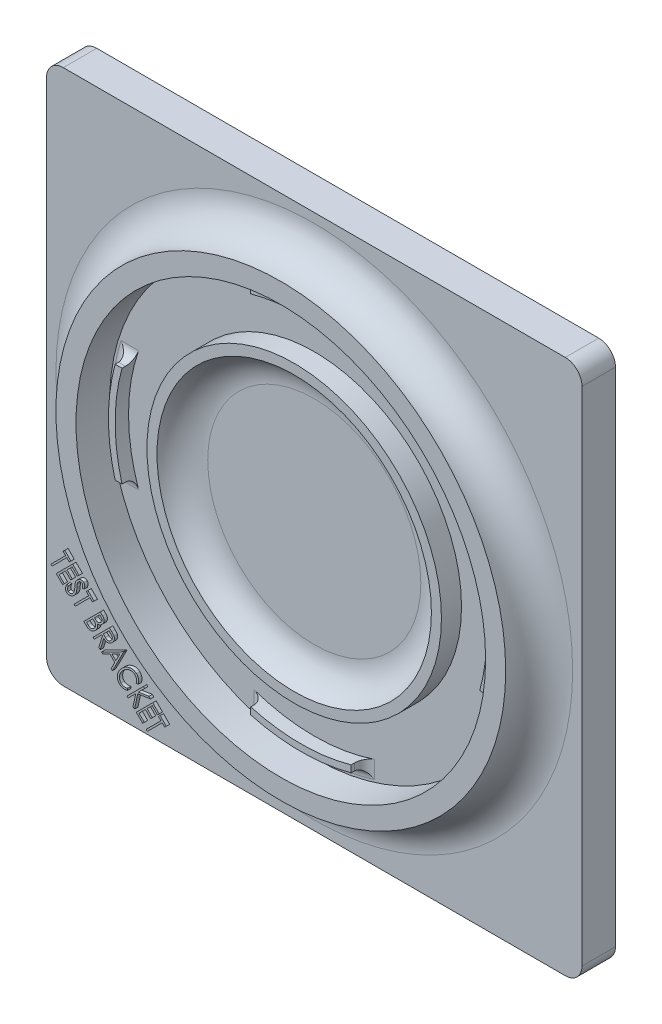
SolidWorks part; units mm, degrees
ref_plane "Front Plane" through (0, 0, 0) normal (0, 0, 1) x (1, 0, 0)
ref_plane "Top Plane" through (0, 0, 0) normal (0, 1, 0) x (1, 0, 0)
ref_plane "Right Plane" through (0, 0, 0) normal (1, 0, 0) x (0, 0, -1)
sketch "Sketch1" plane through (0, 0, 0) normal (0, 0, 1) x (1, 0, 0)
  line L1 (-40, 40) -> (40, 40)
  line L2 (-40, 40) -> (-40, -40)
  line L3 (-40, -40) -> (40, -40)
  line L4 (40, 40) -> (40, -40)
  line L5 (-40, 40) -> (40, -40) construction
  line L6 (-40, -40) -> (40, 40) construction
  point P0 (0, 0)
  dimension "D1" = 80
  dimension "D2" = 80
extrude "Boss-Extrude1" add sketch "Sketch1" along normal blind 5
fillet "Fillet1" radius 2.5 4 edges at (40, 40, 2.5) (-40, 40, 2.5) (40, -40, 2.5) (-40, -40, 2.5)
sketch "Sketch5" plane through (0, 0, 5) normal (0, 0, 1) x (1, 0, 0)
  line L5 (0, 29) -> (0, 27.75) construction
  line L6 (-7.5, 29) -> (7.5, 29)
  line L11 (-7.5, 29) -> (-7.5, -29)
  line L12 (-7.5, -29) -> (7.5, -29)
  line L16 (7.5, 29) -> (7.5, -29)
  line L17 (-7.5, 29) -> (7.5, -29) construction
  line L18 (-7.5, -29) -> (7.5, 29) construction
  line L19 (-29, 7.5) -> (29, 7.5)
  line L20 (-29, 7.5) -> (-29, -7.5)
  line L21 (-29, -7.5) -> (29, -7.5)
  line L22 (29, 7.5) -> (29, -7.5)
  line L23 (-29, 7.5) -> (29, -7.5) construction
  line L24 (-29, -7.5) -> (29, 7.5) construction
  line L26 (-2, 29.0722) -> (2, 29.0722)
  line L27 (-2, 29.0722) -> (-2, 27.6778)
  line L28 (-2, 27.6778) -> (2, 27.6778)
  line L29 (2, 29.0722) -> (2, 27.6778)
  line L30 (-2, 29.0722) -> (2, 27.6778) construction
  line L31 (-2, 27.6778) -> (2, 29.0722) construction
  circle A8 centre (0, 0) radius 27.75
  circle A9 centre (0, 0) radius 28.75
  point P14 (0, 28.375)
  dimension "D1" = 57.5
  dimension "D2" = 55.5
  dimension "D3" = 15
  dimension "D4" = 58
  dimension "D5" = 15
  dimension "D6" = 58
  dimension "D7" = 4
extrude "Boss-Extrude5" add sketch "Sketch5" along normal blind 2 contours L19 A9 L21 A8 | L27 A9 L11 A8 | L16 A9 L29 A8 | A9 L19 A8 L21 | L11 A9 L16 A8 region at (-4.7656, 27.7983, 5) region at (-27.9111, 0, 5) region at (4.7656, 27.7983, 5) region at (0, -27.9111, 5) region at (27.9111, 0, 5)
sketch "Sketch12" plane through (0, 0, 5) normal (0, 0, 1) x (1, 0, 0)
  circle A0 centre (0, 0) radius 30.6
  circle A1 centre (0, 0) radius 33.6
  dimension "D1" = 61.2
  dimension "D2" = 67.2
extrude "Boss-Extrude8" add sketch "Sketch12" along normal blind 5
sketch "Sketch13" plane through (0, 0, 5) normal (0, 0, 1) x (1, 0, 0)
  circle A0 centre (0, 0) radius 20.5
  circle A1 centre (0, 0) radius 22
  dimension "D1" = 44
  dimension "D2" = 41
extrude "Boss-Extrude9" add sketch "Sketch13" along normal blind 3
fillet "Fillet2" radius 1.5 15 edges at (28.75, 0, 5) (0, -28.75, 5) (-28.75, 0, 5) (4.7725, 28.3511, 5) (-4.7725, 28.3511, 5) (7.5, -27.2359, 5) (-7.5, -27.2359, 5) (-27.2359, -7.5, 5) (-27.2359, 7.5, 5) (27.2359, 7.5, 5) (27.2359, -7.5, 5) (7.5, 27.2359, 5) (2, 28.1791, 5) (-2, 28.1791, 5) (-7.5, 27.2359, 5)
fillet "Fillet3" radius 5 2 edges at (33.6, 0, 5) (20.5, 0, 5)
sketch "Sketch14" plane through (0, 0, 5) normal (0, 0, 1) x (1, 0, 0)
  line L0 (-39.2678, -24.2678) -> (-24.2678, -39.2678) construction
  text T0 "TEST BRACKET" font "Century Gothic" height 3.5
extrude "Boss-Extrude10" add sketch "Sketch14" along normal blind 0.5
